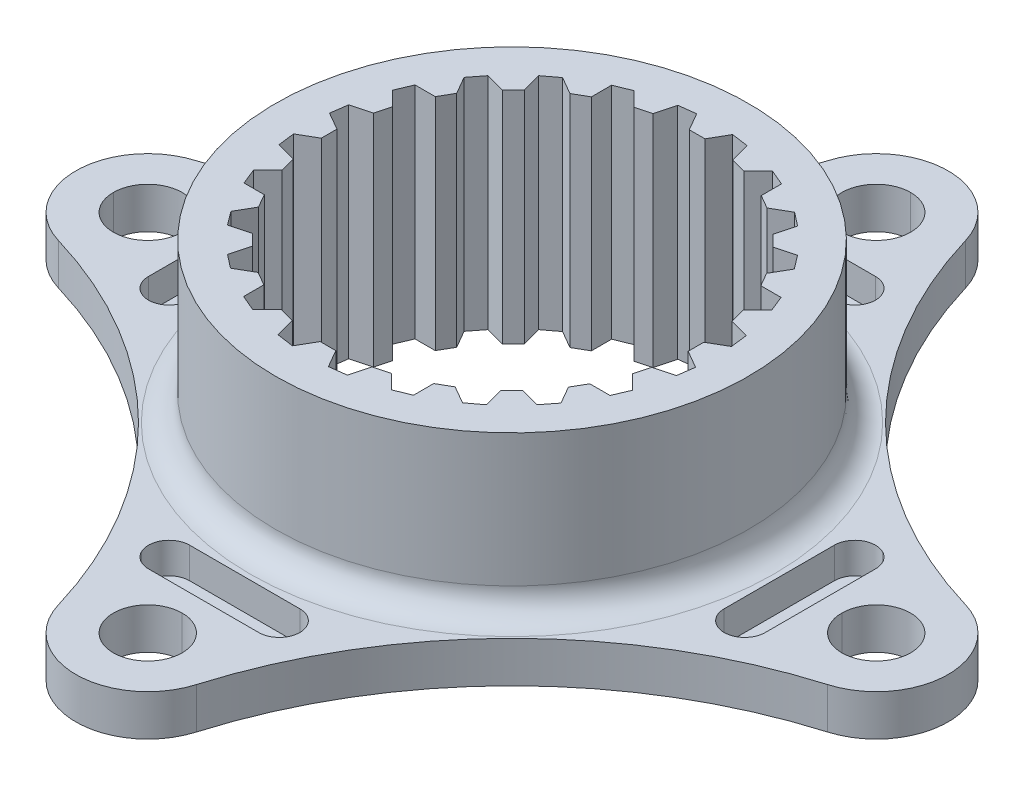
SolidWorks part; units mm, degrees
note: '?' marks a value the reader was unsure of. The reader was unsure of these and kept them because the rebuilt part matched: shared geometry of "Sketch6<5>".
material "7075-T6 (SN)"
ref_plane "Front Plane" through (0, 0, 0) normal (0, 0, 1) x (1, 0, 0)
ref_plane "Top Plane" through (0, 0, 0) normal (0, 1, 0) x (1, 0, 0)
ref_plane "Right Plane" through (0, 0, 0) normal (1, 0, 0) x (0, 0, -1)
sketch "Sketch1" plane through (0, 0, 0) normal (0, 1, 0) x (1, 0, 0)
  line L0 (274.6284, 454.6081) -> (780.6456, 454.6081) construction
  circle A0 centre (0, 0) radius 23
  dimension "D1" = 46
sketch "Sketch5" plane through (0, 0, 0) normal (0, 1, 0) x (1, 0, 0)
  circle A0 centre (0, 0) radius 23
  circle A1 centre (0, 0) radius 25
  dimension "D1" = 46
  dimension "D2" = 50
sketch "Sketch6" plane through (0, 0, 0) normal (0, 1, 0) x (1, 0, 0)
  line L0 (-0.9689, -22.7363) -> (0.9689, -22.7363)
  line L1 (0.9689, -22.7363) -> (2.2189, -24.9013)
  line L2 (0, 33.3652) -> (0, -36.4848) construction
  line L3 (-0.9689, -22.7363) -> (-2.2189, -24.9013)
  line L4 (-4.9456, -22.1943) -> (-4.2985, -24.6091)
  line L5 (-6.8174, -21.6927) -> (-4.9456, -22.1943)
  line L6 (-6.8174, -21.6927) -> (-8.5852, -23.4605)
  line L7 (-10.5182, -22.6399) -> (-8.5852, -23.4605)
  line L8 (-10.5182, -20.1399) -> (-10.5182, -22.6399)
  line L9 (-12.1965, -19.171) -> (-10.5182, -20.1399)
  line L10 (-12.1965, -19.171) -> (-14.3615, -20.421)
  line L11 (-16.0164, -19.1281) -> (-14.3615, -20.421)
  line L12 (-15.3693, -16.7133) -> (-16.0164, -19.1281)
  line L13 (-16.7396, -15.343) -> (-15.3693, -16.7133)
  line L14 (-16.7396, -15.343) -> (-19.1544, -15.99)
  line L15 (-20.4182, -14.3129) -> (-19.1544, -15.99)
  line L16 (-19.1682, -12.1478) -> (-20.4182, -14.3129)
  line L17 (-20.1372, -10.4696) -> (-19.1682, -12.1478)
  line L18 (-20.1372, -10.4696) -> (-22.6372, -10.4696)
  line L19 (-23.4239, -8.5225) -> (-22.6372, -10.4696)
  line L20 (-21.6561, -6.7547) -> (-23.4239, -8.5225)
  line L21 (-22.1576, -4.8829) -> (-21.6561, -6.7547)
  line L22 (-22.1576, -4.8829) -> (-24.5725, -4.2358)
  line L23 (-24.8284, -2.1515) -> (-24.5725, -4.2358)
  line L24 (-22.6633, -0.9015) -> (-24.8284, -2.1515)
  line L25 (-22.6633, 1.0364) -> (-22.6633, -0.9015)
  line L26 (-22.6633, 1.0364) -> (-24.8284, 2.2864)
  line L27 (-24.5361, 4.366) -> (-24.8284, 2.2864)
  line L28 (-22.1213, 5.013) -> (-24.5361, 4.366)
  line L29 (-21.6197, 6.8849) -> (-22.1213, 5.013)
  line L30 (-21.6197, 6.8849) -> (-23.3875, 8.6526)
  line L31 (-22.567, 10.5857) -> (-23.3875, 8.6526)
  line L32 (-20.067, 10.5857) -> (-22.567, 10.5857)
  line L33 (-19.098, 12.2639) -> (-20.067, 10.5857)
  line L34 (-19.098, 12.2639) -> (-20.348, 14.429)
  line L35 (-19.0552, 16.0838) -> (-20.348, 14.429)
  line L36 (-16.6403, 15.4368) -> (-19.0552, 16.0838)
  line L37 (-15.27, 16.8071) -> (-16.6403, 15.4368)
  line L38 (-15.27, 16.8071) -> (-15.9171, 19.2219)
  line L39 (-14.24, 20.4857) -> (-15.9171, 19.2219)
  line L40 (-12.0749, 19.2357) -> (-14.24, 20.4857)
  line L41 (-10.3966, 20.2046) -> (-12.0749, 19.2357)
  line L42 (-10.3966, 20.2046) -> (-10.3966, 22.7046)
  line L43 (-8.4496, 23.4913) -> (-10.3966, 22.7046)
  line L44 (-6.6818, 21.7235) -> (-8.4496, 23.4913)
  line L45 (-4.8099, 22.2251) -> (-6.6818, 21.7235)
  line L46 (-4.8099, 22.2251) -> (-4.1629, 24.6399)
  line L47 (-2.0785, 24.8958) -> (-4.1629, 24.6399)
  line L48 (-0.8285, 22.7308) -> (-2.0785, 24.8958)
  line L49 (1.1093, 22.7308) -> (-0.8285, 22.7308)
  line L50 (1.1093, 22.7308) -> (2.3593, 24.8958)
  line L51 (4.4389, 24.6036) -> (2.3593, 24.8958)
  line L52 (5.086, 22.1888) -> (4.4389, 24.6036)
  line L53 (6.9578, 21.6872) -> (5.086, 22.1888)
  line L54 (6.9578, 21.6872) -> (8.7256, 23.455)
  line L55 (10.6586, 22.6344) -> (8.7256, 23.455)
  line L56 (10.6586, 20.1344) -> (10.6586, 22.6344)
  line L57 (12.3369, 19.1655) -> (10.6586, 20.1344)
  line L58 (12.3369, 19.1655) -> (14.5019, 20.4155)
  line L59 (16.1568, 19.1226) -> (14.5019, 20.4155)
  line L60 (15.5097, 16.7078) -> (16.1568, 19.1226)
  line L61 (16.88, 15.3375) -> (15.5097, 16.7078)
  line L62 (16.88, 15.3375) -> (19.2948, 15.9845)
  line L63 (20.5586, 14.3074) -> (19.2948, 15.9845)
  line L64 (19.3086, 12.1424) -> (20.5586, 14.3074)
  line L65 (20.2776, 10.4641) -> (19.3086, 12.1424)
  line L66 (20.2776, 10.4641) -> (22.7776, 10.4641)
  line L67 (23.5643, 8.517) -> (22.7776, 10.4641)
  line L68 (21.7965, 6.7492) -> (23.5643, 8.517)
  line L69 (22.298, 4.8774) -> (21.7965, 6.7492)
  line L70 (22.298, 4.8774) -> (24.7129, 4.2303)
  line L71 (24.9688, 2.146) -> (24.7129, 4.2303)
  line L72 (22.8037, 0.896) -> (24.9688, 2.146)
  line L73 (22.8037, -1.0419) -> (22.8037, 0.896)
  line L74 (22.8037, -1.0419) -> (24.9688, -2.2919)
  line L75 (24.6765, -4.3714) -> (24.9688, -2.2919)
  line L76 (22.2617, -5.0185) -> (24.6765, -4.3714)
  line L77 (21.7601, -6.8903) -> (22.2617, -5.0185)
  line L78 (21.7601, -6.8903) -> (23.5279, -8.6581)
  line L79 (22.7074, -10.5912) -> (23.5279, -8.6581)
  line L80 (20.2074, -10.5912) -> (22.7074, -10.5912)
  line L81 (19.2384, -12.2694) -> (20.2074, -10.5912)
  line L82 (19.2384, -12.2694) -> (20.4884, -14.4345)
  line L83 (19.1955, -16.0893) -> (20.4884, -14.4345)
  line L84 (16.7807, -15.4423) -> (19.1955, -16.0893)
  line L85 (15.4104, -16.8126) -> (16.7807, -15.4423)
  line L86 (15.4104, -16.8126) -> (16.0575, -19.2274)
  line L87 (14.3804, -20.4912) -> (16.0575, -19.2274)
  line L88 (12.2153, -19.2412) -> (14.3804, -20.4912)
  line L89 (10.537, -20.2101) -> (12.2153, -19.2412)
  line L90 (10.537, -20.2101) -> (10.537, -22.7101)
  line L91 (8.59, -23.4968) -> (10.537, -22.7101)
  line L92 (6.8222, -21.729) -> (8.59, -23.4968)
  line L93 (4.9503, -22.2306) -> (6.8222, -21.729)
  line L94 (4.9503, -22.2306) -> (4.3033, -24.6454)
  line L95 (2.2189, -24.9013) -> (4.3033, -24.6454)
  line L96 (-4.2985, -24.6091) -> (-2.2189, -24.9013)
  circle A0 centre (0, 0) radius 23 construction
  circle A1 centre (0, 0) radius 25 construction
  point P11 (0, -23)
  point P131 (0.0702, -0.0027)
  dimension "D4" = 2.5
  dimension "D1" = 2.1
  dimension "D5" = 112
  dimension "D6" = 120
  dimension "D2" = 1.9379
  dimension "D3" = 24
sketch "Sketch8" plane through (0, 0, 0) normal (0, 1, 0) x (1, 0, 0)
  circle A0 centre (0, 0) radius 100
  dimension "D1" = 200
extrude "Boss-Extrude4" add sketch "Sketch8" along normal blind 24.638 contours A0
extrude "Cut-Extrude1" cut sketch "Sketch6" along normal through all
sketch "Sketch9" plane through (0, 24.638, 0) normal (0, 1, 0) x (1, 0, 0)
  circle A0 centre (0, 0) radius 29.21
  dimension "D1" = 58.42
extrude "Cut-Extrude3" cut sketch "Sketch9" against normal blind 19.558 flip side to cut
sketch "Sketch10" plane through (0, 5.08, 0) normal (0, 1, 0) x (1, 0, 0)
  circle A1 centre (0, 45) radius 4.2545
  circle A4 centre (45, 0) radius 4.2545
  circle A5 centre (0, -45) radius 4.2545
  circle A6 centre (-45, 0) radius 4.2545
  point P11 (0, 0)
  point P28 (0, 0)
  dimension "D1" = 4
  dimension "D2" = 8.509
  dimension "D3" = 45
sketch "Sketch11" plane through (0, 5.08, 0) normal (0, 1, 0) x (1, 0, 0)
  line L2 (0, 45) -> (8.89, 45) construction
  line L3 (0, 45) -> (8.5239, 47.5249) construction
  circle A0 centre (45, 0) radius 8.89
  circle A1 centre (0, -45) radius 8.89
  circle A2 centre (-45, 0) radius 8.89
  arc A3 (8.5239, 47.5249) -> (47.5249, 8.5239) centre (63.9398, 63.9398) ccw
  arc A4 (47.5249, -8.5239) -> (8.5239, -47.5249) centre (63.9398, -63.9398) ccw
  arc A5 (-8.5239, -47.5249) -> (-47.5249, -8.5239) centre (-63.9398, -63.9398) ccw
  arc A6 (-47.5249, 8.5239) -> (-8.5239, 47.5249) centre (-63.9398, 63.9398) ccw
  circle A8 centre (0, 45) radius 8.89
  point P12 (0, 0)
  point P25 (0, 0)
  dimension "D4" = 4
  dimension "D1" = 4
  dimension "D2" = 17.78
  dimension "D3" = 16.5
extrude "Cut-Extrude6" cut sketch "Sketch11" against normal blind 7.62
extrude "Cut-Extrude7" cut sketch "Sketch10" against normal blind 7.62
fillet "Fillet2" radius 3.175 1 edges at (0, 5.08, 29.21)
ref_plane "Plane1" through (0, 0, 0) normal (0, 0, 1) x (1, 0, 0)
ref_plane "Plane2" through (0, 0, 0) normal (-1, 0, 0) x (0, 0, 1)
split line "Split Line1"
split line "Split Line2"
ref_axis "Axis1" through (0, 5.334, 0) along (0, -1, 0)?
sketch "Sketch13" plane through (0, 5.08, 0) normal (0, 1, 0) x (1, 0, 0)
  line L0 (0, 2.794) -> (0, -2.794) construction
  line L1 (-8.4262, 38.1) -> (8.4262, 38.1)
  line L2 (-8.4262, 38.1) -> (-10.795, 33.02)
  line L3 (-10.795, 33.02) -> (10.795, 33.02)
  line L4 (8.4262, 38.1) -> (10.795, 33.02)
  point P11 (0, 33.02)
  dimension "D1" = 115
  dimension "D2" = 115
  dimension "D3" = 5.08
  dimension "D4" = 0
  dimension "D5" = 21.59
  dimension "D6" = 33.02
extrude "Cut-Extrude12" cut sketch "Sketch13" against normal blind 3.81 contours L1 L4 L3 L2
fillet "Fillet5" radius 2.54 4 edges at (-10.795, 3.175, -33.02) (10.795, 3.175, -33.02) (-8.4262, 3.175, -38.1) (8.4262, 3.175, -38.1)
pattern_circular "CirPattern1" count 4 over 360 about axis through (0, 0, 0) along (0, 1, 0) of "Cut-Extrude12", "Fillet5"
sketch "Sketch14" plane through (0, 0, 0) normal (0, -1, 0) x (1, 0, 0)
  circle A0 centre (0, 0) radius 29.0322
  dimension "D1" = 58.0644
extrude "Boss-Extrude5" add sketch "Sketch14" along normal blind 2.54
extrude "Cut-Extrude17" cut sketch "Sketch6<5>" against normal blind 2.54
sketch "Sketch6<5>" plane through (0, 0, 0) normal (0, 1, 0) x (1, 0, 0) same geometry as "Sketch6"
chamfer "Chamfer1" distance 0.508 angle 45 1 edges at (0, -2.54, -29.0322)
